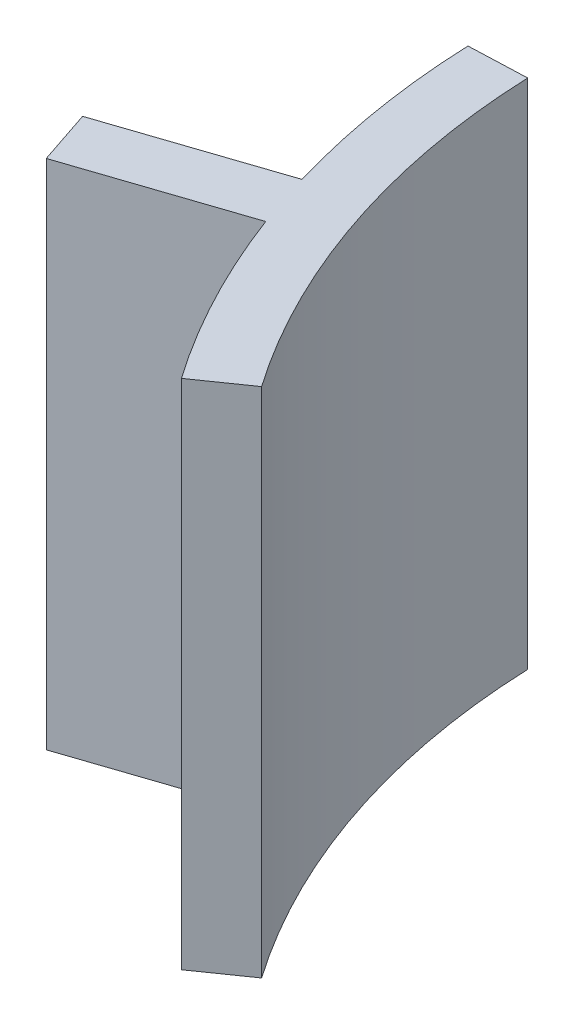
SolidWorks part; units mm, degrees
ref_plane "Front Plane" through (0, 0, 0) normal (0, 0, 1) x (1, 0, 0)
ref_plane "Top Plane" through (0, 0, 0) normal (0, 1, 0) x (1, 0, 0)
ref_plane "Right Plane" through (0, 0, 0) normal (1, 0, 0) x (0, 0, -1)
sketch "Sketch1" plane through (0, 0, 0) normal (0, 1, 0) x (1, 0, 0)
  line L0 (-116.9166, -4.4159) -> (-125.9102, -4.7556) construction
  line L1 (-116.9166, -4.4159) -> (-125.9102, -4.7556)
  line L2 (-103.3353, -72.0958) -> (-95.9542, -66.9461)
  line L4 (-143.6352, -52.8979) -> (-146.4958, -44.3646)
  line L5 (-146.4958, -44.3646) -> (-120.8198, -35.7571)
  line L6 (-143.6352, -52.8979) -> (-117.9592, -44.2903)
  arc A0 (-116.9166, -4.4159) -> (-95.9542, -66.9461) centre (0, 0) ccw
  arc A1 (-125.9102, -4.7556) -> (-120.8198, -35.7571) centre (0, 0) ccw
  arc A2 (-120.8198, -35.7571) -> (-125.9102, -4.7556) centre (0, 0) cw
  arc A3 (-120.8198, -35.7571) -> (-125.9102, -4.7556) centre (0, 0) cw
  arc A4 (-117.9592, -44.2903) -> (-103.3353, -72.0958) centre (0, 0) ccw
  arc A5 (-103.3353, -72.0958) -> (-117.9592, -44.2903) centre (0, 0) cw
  arc A6 (-103.3353, -72.0958) -> (-117.9592, -44.2903) centre (0, 0) cw
  point P4 (0, 0)
  point P5 (0, 0)
  point P8 (0, 0)
  point P13 (-145.0655, -48.6312)
  dimension "D1" = 4.5
extrude "Boss-Extrude1" add sketch "Sketch1" along normal blind 80 contours L6 A4 L2 A0 L1 A1 L5 L4 region at (-118.8915, 0, 39.8567)
sketch "Sketch3" plane through (1.4303, 0, 4.2666) normal (0.3179, 0, 0.9481) x (0.9481, 0, -0.3179)
  line L1 (-153, 80) -> (-145.5, 80) construction
  line L2 (-153, 80) -> (-153, 55) construction
  line L3 (-153, 55) -> (-145.5, 55) construction
  line L4 (-145.5, 80) -> (-145.5, 55) construction
  line L5 (-153, 0) -> (-145.9366, 0) construction
  line L6 (-153, 0) -> (-153, 25) construction
  line L7 (-153, 25) -> (-145.9366, 25) construction
  line L8 (-145.9366, 0) -> (-145.9366, 25) construction
  dimension "D1" = 7.5
  dimension "D2" = 25
  dimension "D3" = 25
